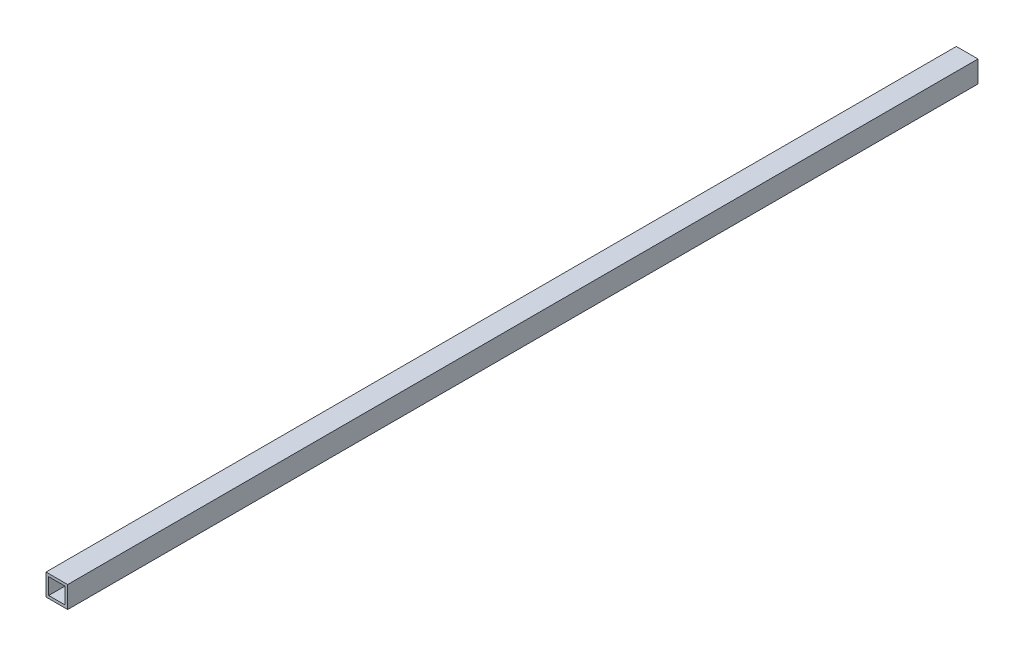
SolidWorks part; units mm, degrees
material "6061 Alloy"
ref_plane "Front Plane" through (0, 0, 0) normal (0, 0, 1) x (1, 0, 0)
ref_plane "Top Plane" through (0, 0, 0) normal (0, 1, 0) x (1, 0, 0)
ref_plane "Right Plane" through (0, 0, 0) normal (1, 0, 0) x (0, 0, -1)
sketch "Sketch1" plane through (0, 0, 0) normal (0, 0, 1) x (1, 0, 0)
  line L0 (12.7, 0) -> (9.525, 0) construction
  line L1 (-12.7, 0) -> (12.7, 0) construction
  line L2 (0, 12.7) -> (0, -12.7)
  point P7 (0, 0)
sketch "Sketch2" plane through (0, 0, 0) normal (1, 0, 0) x (0, 0, -1)
  line L0 (533.4, 0) -> (-533.4, 0)
  point P4 (0, 0)
  dimension "Length" = 1066.8
sketch "Sketch3" plane through (0, 0, 0) normal (0, 0, 1) x (1, 0, 0)
  line L0 (-12.7, 0) -> (12.7, 0) construction
  line L5 (12.7, -12.7) -> (-12.7, -12.7)
  line L6 (12.7, -12.7) -> (12.7, 12.7)
  line L11 (12.7, 12.7) -> (-12.7, 12.7)
  line L12 (-12.7, -12.7) -> (-12.7, 12.7)
  line L14 (12.7, -12.7) -> (-12.7, 12.7) construction
  line L15 (12.7, 12.7) -> (-12.7, -12.7) construction
  line L16 (9.525, -9.525) -> (-9.525, -9.525)
  line L17 (9.525, -9.525) -> (9.525, 9.525)
  line L18 (9.525, 9.525) -> (-9.525, 9.525)
  line L19 (-9.525, -9.525) -> (-9.525, 9.525)
  line L20 (9.525, -9.525) -> (-9.525, 9.525) construction
  line L21 (9.525, 9.525) -> (-9.525, -9.525) construction
  point P0 (0, 0)
  point P5 (0, 0)
  point P13 (9.525, -12.7)
  dimension "D1" = 3.175
extrude "Boss-Extrude1" add sketch "Sketch3" along normal up to vertex (533.4 mm away) and the other way up to vertex (533.4 mm away) up to point (0, 0, 533.4) other way up to point (0, 0, -533.4)
sketch "Sketch5" plane through (0, 0, 0) normal (1, 0, 0) x (0, 0, -1)
  line L0 (-533.4, 0) -> (533.4, 0) construction
  line L3 (-533.4, -12.7) -> (-533.4, 12.7) construction
  line L4 (533.4, -12.7) -> (533.4, 12.7) construction
  point P6 (-504.825, 0)
  point P7 (-495.3, 0)
  point P8 (495.3, 0)
  point P10 (504.825, 0)
  dimension "D1" = 28.575
  dimension "D2" = 38.1
  dimension "D3" = 28.575
  dimension "D4" = 38.1
equation "\"D1@Sketch3\"=\"Wall thickness@Sketch1\""
equation "\"D1@Sketch5\"=\"Width@Sketch1\"*1.125"
equation "\"D2@Sketch5\"=\"Width@Sketch1\"*1.5"
equation "\"D3@Sketch5\"=\"D1@Sketch5\""
equation "\"D4@Sketch5\"=\"D2@Sketch5\""
equation "\"D2@Sketch3\"=\"Wall Thickness@Sketch1\""
